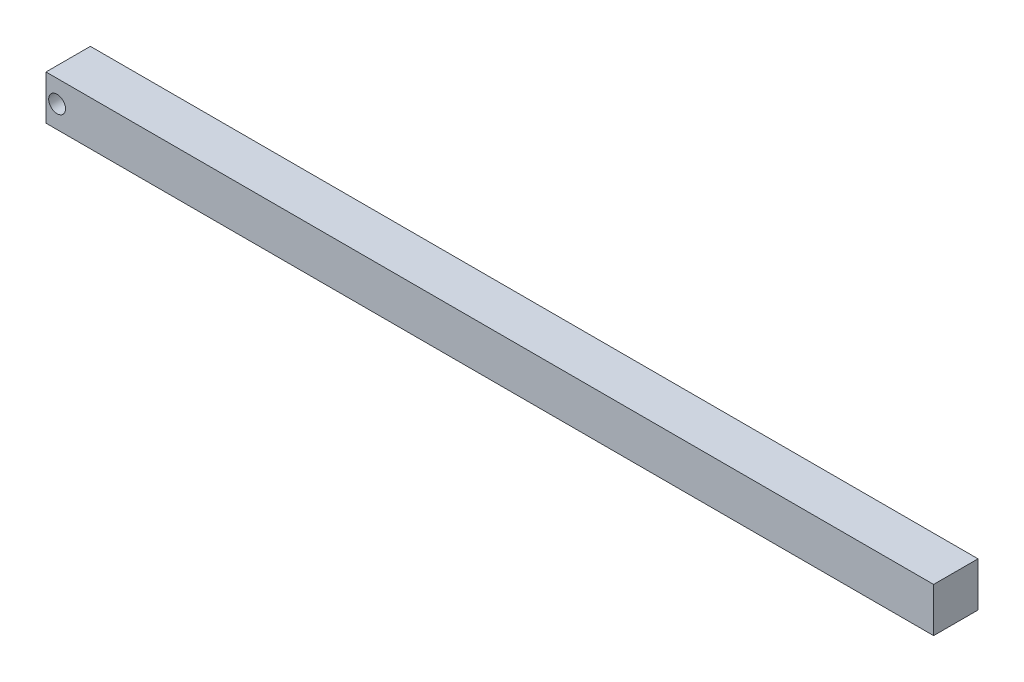
SolidWorks part; units mm, degrees
material "Plain Carbon Steel"
ref_plane "Front Plane" through (0, 0, 0) normal (0, 0, 1) x (1, 0, 0)
ref_plane "Top Plane" through (0, 0, 0) normal (0, 1, 0) x (1, 0, 0)
ref_plane "Right Plane" through (0, 0, 0) normal (1, 0, 0) x (0, 0, -1)
sketch "Sketch1" plane through (0, 0, 0) normal (0, 0, 1) x (1, 0, 0)
  line L0 (-100, -5) -> (100, -5)
  line L1 (100, -5) -> (100, 5)
  line L2 (100, 5) -> (-100, 5)
  line L3 (-100, 5) -> (-100, -5)
extrude "Boss-Extrude1" add sketch "Sketch1" along normal mid plane 10
sketch "Sketch2" plane through (0, 0, 0) normal (0, 0, 1) x (1, 0, 0)
  circle A0 centre (-97.5, 0) radius 1.9
  dimension "D1" = 3.8
extrude "Cut-Extrude1" cut sketch "Sketch2" against normal mid plane 30
